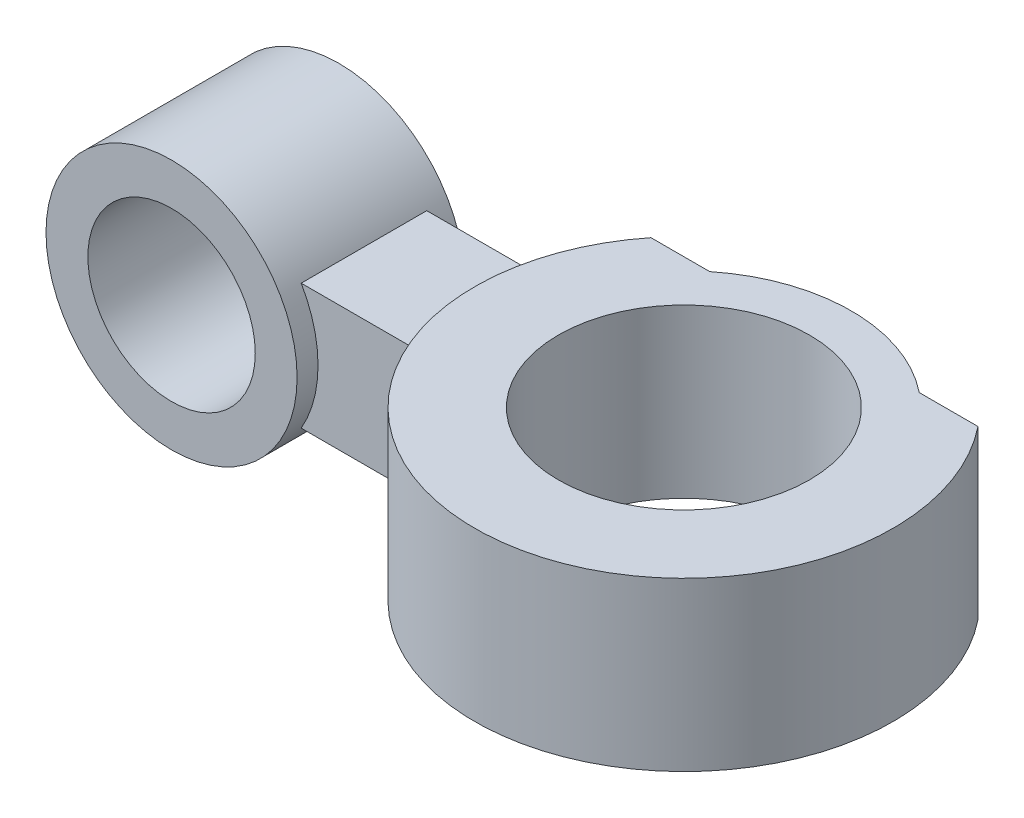
SolidWorks part; units mm, degrees
ref_plane "前视基准面" through (0, 0, 0) normal (0, 0, 1) x (1, 0, 0)
ref_plane "上视基准面" through (0, 0, 0) normal (0, 1, 0) x (1, 0, 0)
ref_plane "右视基准面" through (0, 0, 0) normal (1, 0, 0) x (0, 0, -1)
sketch "草图1" plane through (0, 0, 0) normal (0, 0, 1) x (1, 0, 0)
  circle A0 centre (0, 0) radius 1
  circle A1 centre (0, 0) radius 1.5
extrude "凸台-拉伸1" add sketch "草图1" along normal blind 2
ref_plane "基准面4" through (0, 0, 1) normal (0, 0, 1) x (1, 0, 0)
sketch "草图2" plane through (0, 0, 1) normal (0, 0, 1) x (1, 0, 0)
  line L0 (0, 0) -> (3, 0)
  line L3 (5.1213, 0) -> (3, 0)
  dimension "D1" = 3
sketch "草图3" plane through (0, 0, 2) normal (0, 0, 1) x (1, 0, 0)
  line L0 (0, 0) -> (0.3446, 0)
  line L1 (0, 0) -> (3, 0) construction
sketch "草图4" plane through (0, 0, 0) normal (0, 0, -1) x (-1, 0, 0)
  line L0 (0, 0) -> (-0.3446, 0)
ref_plane "基准面5" through (0, 0, 0) normal (0, 1, 0) x (1, 0, 0)
sketch "草图6" plane through (0, 0, 0) normal (0, 1, 0) x (1, 0, 0)
  line L0 (5.1213, -1) -> (3, -1) construction
  line L2 (6.3729, 0.56) -> (7.0749, 0.56)
  line L3 (3.8698, 0.56) -> (3.1678, 0.56)
  circle A0 centre (5.1213, -1) radius 1.5
  arc A1 (6.3729, 0.56) -> (3.8698, 0.56) centre (5.1213, -1) ccw
  arc A2 (3.1678, 0.56) -> (7.0749, 0.56) centre (5.1213, -1) ccw
extrude "凸台-拉伸2" add sketch "草图6" along normal mid plane 2 separate body
sketch "草图8" plane through (0, 0, 1) normal (0, 0, 1) x (1, 0, 0)
  line L0 (1.299, 0.75) -> (1.7718, 0.75)
  line L4 (1.7718, 0.75) -> (1.7718, -0.75)
  line L7 (1.3813, 0.5847) -> (1.7718, 0.75) construction
  line L8 (1.3813, -0.5847) -> (1.7718, -0.75) construction
  line L9 (1.299, -0.75) -> (1.7718, -0.75)
  arc A1 (1.299, -0.75) -> (1.299, 0.75) centre (0, 0) ccw
  dimension "D1" = 1.5
extrude "凸台-拉伸3" add sketch "草图8" along normal mid plane 1.5
ref_axis "基准轴1" through (1.65, 0, 1) along (-1, 0, 0)
ref_point "点1"
sketch "草图10" plane through (1.7718, 0, 0) normal (1, 0, 0) x (0, 0, -1)
  line L1 (-1.75, 0.75) -> (-0.25, 0.75)
  line L2 (-1.75, 0.75) -> (-1.75, -0.75)
  line L3 (-1.75, -0.75) -> (-0.25, -0.75)
  line L4 (-0.25, 0.75) -> (-0.25, -0.75)
  line L5 (-1.75, 0.75) -> (-0.25, -0.75) construction
  line L6 (-1.75, -0.75) -> (-0.25, 0.75) construction
  point P0 (-1, 0)
extrude "凸台-拉伸4" add sketch "草图10" along normal up to body separate body
